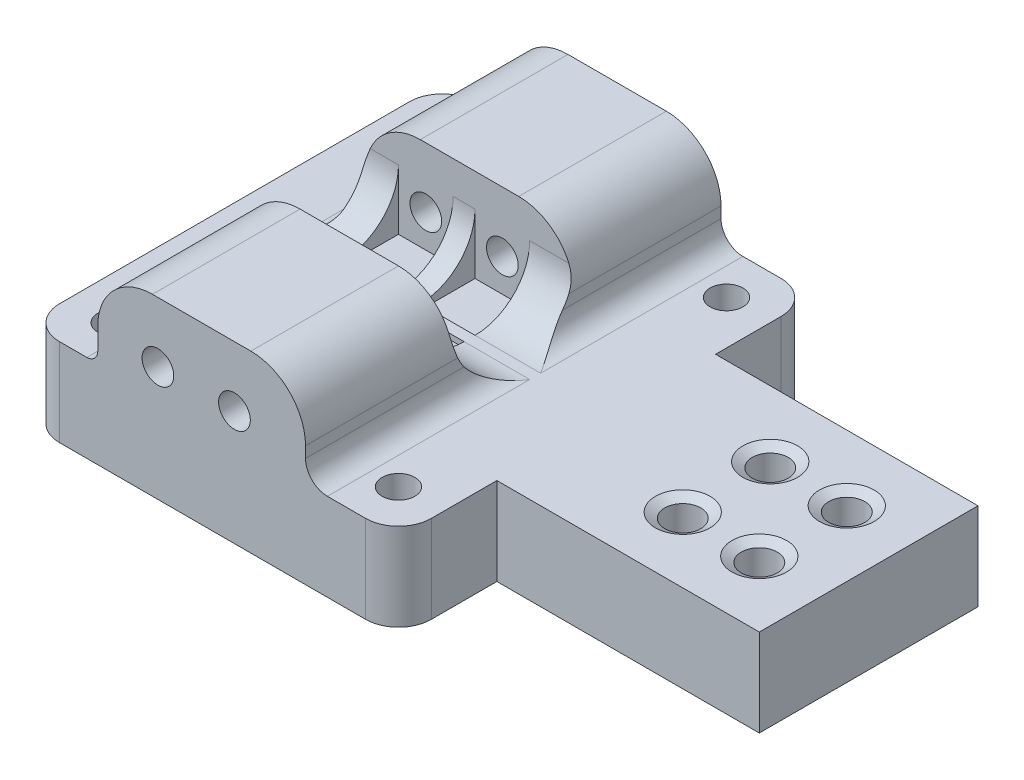
SolidWorks part; units mm, degrees
ref_plane "Front" through (0, 0, 0) normal (0, 0, 1) x (1, 0, 0)
ref_plane "Top" through (0, 0, 0) normal (0, 1, 0) x (1, 0, 0)
ref_plane "Right" through (0, 0, 0) normal (1, 0, 0) x (0, 0, -1)
sketch "Sketch1" plane through (0, 0, 0) normal (0, 1, 0) x (1, 0, 0)
  line L1 (0, 0) -> (300, 0)
  line L2 (0, 0) -> (0, -20)
  line L3 (0, -20) -> (300, -20)
  line L4 (300, 0) -> (300, -20)
  dimension "D1" = 20
  dimension "D2" = 300
extrude "Boss-Extrude1" add sketch "Sketch1" along normal blind 8
sketch "Sketch2" plane through (0, 0, 20) normal (0, 0, 1) x (1, 0, 0)
  line L0 (0, 8) -> (300, 8) construction
  line L1 (0, 0) -> (34, 0)
  line L2 (0, 0) -> (0, 8)
  line L3 (0, 8) -> (34, 8)
  line L4 (34, 0) -> (34, 8)
  line L5 (266, 8) -> (300, 8)
  line L6 (300, 0) -> (300, 8)
  line L7 (266, 0) -> (300, 0)
  line L8 (266, 0) -> (266, 8)
  dimension "D1" = 34
  dimension "D2" = 2
extrude "Boss-Extrude2" add sketch "Sketch2" along normal blind 9
sketch "Sketch3" plane through (0, 0, 0) normal (0, 0, -1) x (-1, 0, 0)
  line L0 (-300, 8) -> (0, 8) construction
  line L1 (0, 0) -> (-34, 0)
  line L2 (0, 0) -> (0, 8)
  line L3 (0, 8) -> (-34, 8)
  line L4 (-34, 0) -> (-34, 8)
  line L5 (-300, 0) -> (-300, 8)
  line L6 (-266, 8) -> (-300, 8)
  line L7 (-266, 0) -> (-266, 8)
  line L8 (-266, 0) -> (-300, 0)
  dimension "D1" = 34
  dimension "D2" = 2
extrude "Boss-Extrude3" add sketch "Sketch3" along normal blind 9
sketch "Sketch4" plane through (0, 8, 0) normal (0, 1, 0) x (1, 0, 0)
  line L0 (0, 9) -> (34, 9) construction
  line L1 (0, 9) -> (0, -29) construction
  circle A0 centre (4, 5) radius 1.5
  circle A1 centre (30, 5) radius 1.5
  circle A2 centre (30, -25) radius 1.5
  circle A3 centre (4, -25) radius 1.5
  circle A4 centre (296, -25) radius 1.5
  circle A5 centre (296, 5) radius 1.5
  circle A6 centre (270, -25) radius 1.5
  circle A7 centre (270, 5) radius 1.5
  dimension "D1" = 3
  dimension "D2" = 4
  dimension "D3" = 4
  dimension "D4" = 2
  dimension "D5" = 2
  dimension "D6" = 2
extrude "Cut-Extrude1" cut sketch "Sketch4" against normal through all
sketch "Sketch5" plane through (0, 0, 20) normal (0, 0, 1) x (1, 0, 0)
  line L0 (34, 8) -> (266, 8) construction
  line L1 (266, 0) -> (241, 0)
  line L2 (266, 0) -> (266, 8)
  line L3 (266, 8) -> (241, 8)
  line L4 (241, 0) -> (241, 8)
  dimension "D1" = 25
extrude "Boss-Extrude4" add sketch "Sketch5" along normal blind 17
sketch "Sketch6" plane through (0, 0, 0) normal (0, 0, -1) x (-1, 0, 0)
  line L0 (-266, 0) -> (-34, 0) construction
  line L1 (-266, 8) -> (-241, 8)
  line L2 (-266, 8) -> (-266, 0)
  line L3 (-266, 0) -> (-241, 0)
  line L4 (-241, 8) -> (-241, 0)
  dimension "D1" = 25
extrude "Boss-Extrude5" add sketch "Sketch6" along normal blind 17
sketch "Sketch12" plane through (0, 0, 37) normal (0, 0, 1) x (1, 0, 0)
  line L0 (241, 0) -> (266, 0) construction
  line L1 (241, 8) -> (249, 8)
  line L2 (241, 8) -> (241, 0)
  line L3 (241, 0) -> (249, 0)
  line L4 (249, 8) -> (249, 0)
  dimension "D1" = 8
extrude "Boss-Extrude7" add sketch "Sketch12" along normal blind 17
sketch "Sketch14" plane through (0, 0, 29) normal (0, 0, 1) x (1, 0, 0)
  line L0 (300, 8) -> (266, 8) construction
  line L1 (294.975, 8) -> (275, 8)
  line L2 (294.975, 8) -> (294.975, -5)
  line L3 (294.975, -5) -> (275, -4)
  line L4 (275, 8) -> (275, -4)
  line L7 (266, 8) -> (266, 0) construction
  dimension "D1" = 20
  dimension "D2" = 9
  dimension "D3" = 13
  dimension "D4" = 12
extrude "Boss-Extrude8" add sketch "Sketch14" along normal blind 12
sketch "Sketch15" plane through (294.975, 0, 0) normal (1, 0, 0) x (0, 0, -1)
  line L0 (-41, -5) -> (-41, 8) construction
  line L2 (-41, -5) -> (-29, -5) construction
  circle A0 centre (-35, 0) radius 1.6
  dimension "D1" = 3.2
  dimension "D2" = 6
  dimension "D3" = 5
extrude "Cut-Extrude7" cut sketch "Sketch15" against normal blind 20
sketch "Sketch16" plane through (0, 0, -9) normal (0, 0, -1) x (-1, 0, 0)
  line L0 (-266, 8) -> (-300, 8) construction
  line L1 (-295, 8) -> (-275, 8)
  line L2 (-295, 8) -> (-295, -5)
  line L3 (-295, -5) -> (-275, -5)
  line L4 (-275, 8) -> (-275, -5)
  line L6 (-266, 0) -> (-266, 8) construction
  dimension "D1" = 20
  dimension "D2" = 9
  dimension "D3" = 13
extrude "Boss-Extrude9" add sketch "Sketch16" along normal blind 12
sketch "Sketch17" plane through (295, 0, 0) normal (1, 0, 0) x (0, 0, -1)
  line L0 (21, -5) -> (9, -5) construction
  line L1 (21, 8) -> (21, -5) construction
  circle A0 centre (15, 0) radius 1.6
  dimension "D1" = 3.2
  dimension "D2" = 5
  dimension "D3" = 6
extrude "Cut-Extrude8" cut sketch "Sketch17" against normal blind 20
sketch "Sketch22" plane through (0, 8, 0) normal (0, 1, 0) x (1, 0, 0)
  line L0 (241, 17) -> (241, 0) construction
  line L1 (259, 9) -> (249, 9)
  line L2 (259, 9) -> (259, -29)
  line L3 (259, -29) -> (249, -29)
  line L4 (249, 9) -> (249, -29)
  line L5 (241, 17) -> (266, 17) construction
  line L6 (266, -37) -> (249, -37) construction
  dimension "D1" = 8
  dimension "D2" = 10
  dimension "D3" = 8
  dimension "D4" = 8
extrude "Cut-Extrude11" cut sketch "Sketch22" against normal through all
sketch "Sketch23" plane through (0, 0, 0) normal (0, -1, 0) x (-1, 0, 0)
  line L0 (-259, -29) -> (-259, 9) construction
  line L1 (-259, -19) -> (-267, -19)
  line L2 (-259, -19) -> (-259, -1)
  line L3 (-259, -1) -> (-267, -1)
  line L4 (-267, -19) -> (-267, -1)
  line L5 (-249, -29) -> (-259, -29) construction
  dimension "D1" = 8
  dimension "D2" = 10
  dimension "D3" = 10
extrude "Cut-Extrude12" cut sketch "Sketch23" against normal blind 4
sketch "Sketch24" plane through (259, 0, 0) normal (-1, 0, 0) x (0, 0, 1)
  line L0 (-9, 0) -> (-9, 8)
  line L1 (-9, 8) -> (-1, 8)
  line L2 (29, 8) -> (-9, 8) construction
  line L3 (-1, 8) -> (-9, 0)
  line L4 (29, 0) -> (29, 8)
  line L5 (29, 8) -> (21, 8)
  line L6 (21, 8) -> (29, 0)
  dimension "D1" = 8
  dimension "D2" = 8
extrude "Boss-Extrude12" add sketch "Sketch24" along normal blind 10
sketch "Sketch25" plane through (267, 0, 0) normal (-1, 0, 0) x (0, 0, 1)
  line L0 (19, 0) -> (19, 4)
  line L1 (19, 4) -> (15, 4)
  line L2 (1, 4) -> (19, 4) construction
  line L3 (15, 4) -> (19, 0)
  line L4 (1, 4) -> (5, 4)
  line L5 (5, 4) -> (1, 0)
  line L6 (1, 0) -> (1, 4)
  dimension "D1" = 4
  dimension "D2" = 4
extrude "Boss-Extrude13" add sketch "Sketch25" along normal blind 8
sketch "Sketch26" plane through (0, 8, 0) normal (0, 1, 0) x (1, 0, 0)
  line L0 (249, 1) -> (249, -21) construction
  line L1 (241, -54) -> (249, -54)
  line L2 (241, -54) -> (241, -6)
  line L3 (241, -6) -> (249, -6)
  line L4 (249, -54) -> (249, -6)
  dimension "D1" = 48
extrude "Boss-Extrude14" add sketch "Sketch26" along normal blind 14
sketch "Sketch27" plane through (0, 8, 0) normal (0, 1, 0) x (1, 0, 0)
  line L0 (249, -21) -> (259, -21) construction
  line L1 (249, -37) -> (257, -37)
  line L2 (249, -37) -> (249, -21)
  line L3 (249, -21) -> (257, -21)
  line L4 (257, -37) -> (257, -21)
  dimension "D1" = 8
extrude "Boss-Extrude15" add sketch "Sketch27" along normal blind 14
sketch "Sketch28" plane through (0, 0, 0) normal (0, -1, 0) x (1, 0, 0)
  line L0 (249, -9) -> (249, 29) construction
  line L1 (241, 54) -> (249, 54)
  line L2 (241, 54) -> (241, 14)
  line L3 (241, 14) -> (249, 14)
  line L4 (249, 54) -> (249, 14)
  dimension "D1" = 40
extrude "Cut-Extrude13" cut sketch "Sketch28" against normal blind 14
sketch "Sketch30" plane through (257, 0, 0) normal (1, 0, 0) x (0, 0, -1)
  line L0 (-37, 22) -> (-21, 22) construction
  line L1 (-21, 22) -> (-37, 22)
  line L2 (-21, 22) -> (-21, 8)
  line L3 (-21, 8) -> (-37, 8)
  line L4 (-37, 22) -> (-37, 8)
extrude "Boss-Extrude16" add sketch "Sketch30" along normal blind 9
sketch "Sketch31" plane through (0, 0, 0) normal (0, -1, 0) x (-1, 0, 0)
  line L1 (-249, -37) -> (-266, -37)
  line L2 (-249, -37) -> (-249, -29)
  line L3 (-249, -29) -> (-266, -29)
  line L4 (-266, -37) -> (-266, -29)
extrude "Cut-Extrude14" cut sketch "Sketch31" against normal blind 5
sketch "Sketch32" plane through (266, 0, 0) normal (1, 0, 0) x (0, 0, -1)
  line L0 (-37, 5) -> (-37, 22) construction
  line L1 (-21, 22) -> (-37, 22)
  line L2 (-21, 22) -> (-21, 13)
  line L3 (-21, 13) -> (-37, 13)
  line L4 (-37, 22) -> (-37, 13)
  dimension "D1" = 9
extrude "Cut-Extrude15" cut sketch "Sketch32" against normal blind 9
sketch "Sketch33" plane through (249, 0, 0) normal (-1, 0, 0) x (0, 0, 1)
  line L0 (29, 5) -> (24, 5)
  line L1 (21, 8) -> (29, 0) construction
  line L2 (24, 5) -> (29, 0)
  line L3 (29, 0) -> (29, 5)
extrude "Cut-Extrude16" cut sketch "Sketch33" against normal blind 10
sketch "Sketch34" plane through (0, 0, 29) normal (0, 0, 1) x (1, 0, 0)
  line L1 (266, 5) -> (259, 5)
  line L2 (266, 5) -> (266, 0)
  line L3 (266, 0) -> (259, 0)
  line L4 (259, 5) -> (259, 0)
extrude "Cut-Extrude17" cut sketch "Sketch34" against normal blind 5
sketch "Sketch35" plane through (0, 0, 21) normal (0, 0, -1) x (-1, 0, 0)
  line L0 (-249, 8) -> (-259, 8) construction
  line L1 (-259, 8) -> (-266, 8)
  line L2 (-259, 8) -> (-259, 13)
  line L3 (-259, 13) -> (-266, 13)
  line L4 (-266, 8) -> (-266, 13)
  line L5 (-266, 8) -> (-259, 8) construction
  line L6 (-266, 8) -> (-266, 13) construction
extrude "Boss-Extrude17" add sketch "Sketch35" along normal blind 5
sketch "Sketch36" plane through (0, 22, 0) normal (0, 1, 0) x (1, 0, 0)
  line L0 (241, -54) -> (249, -54) construction
  line L1 (249, -54) -> (249, -37) construction
  circle A0 centre (245, -50) radius 1.7
  circle A1 centre (245, -18) radius 1.7
  dimension "D1" = 3.4
  dimension "D2" = 4
  dimension "D3" = 4
  dimension "D4" = 2
extrude "Cut-Extrude18" cut sketch "Sketch36" against normal through all
sketch "Sketch37" plane through (0, 8, 0) normal (0, 1, 0) x (1, 0, 0)
  line L0 (241, -6) -> (171, -6)
  line L1 (241, -6) -> (241, -14) construction
  line L2 (241, -6) -> (241, -14)
  line L3 (241, -14) -> (241, -20) construction
  line L4 (241, -14) -> (171, -14)
  line L5 (171, -14) -> (171, -6)
  dimension "D1" = 70
extrude "Boss-Extrude18" add sketch "Sketch37" along normal blind 5
sketch "Sketch39" plane through (0, 8, 0) normal (0, 1, 0) x (1, 0, 0)
  line L0 (34, -20) -> (241, -20) construction
  line L1 (241, -14) -> (175, -14)
  line L2 (241, -14) -> (241, -20)
  line L3 (241, -20) -> (175, -20)
  line L4 (175, -14) -> (175, -20)
  dimension "D1" = 66
extrude "Cut-Extrude19" cut sketch "Sketch39" against normal through all
sketch "Sketch46" plane through (0, 8, 0) normal (0, 1, 0) x (1, 0, 0)
  line L1 (295, 9) -> (275, 9)
  line L2 (295, 9) -> (295, 21)
  line L3 (295, 21) -> (275, 21)
  line L4 (275, 9) -> (275, 21)
  line L5 (294.975, -41) -> (275, -41)
  line L6 (294.975, -41) -> (294.975, -29)
  line L7 (294.975, -29) -> (275, -29)
  line L8 (275, -41) -> (275, -29)
extrude "Boss-Extrude23" add sketch "Sketch46" along normal blind 10
sketch "Sketch47" plane through (0, 18, 0) normal (0, 1, 0) x (1, 0, 0)
  line L0 (295, 21) -> (275, 21) construction
  line L1 (275, 21) -> (303, 21)
  line L2 (275, 21) -> (275, 9)
  line L3 (275, 9) -> (303, 9)
  line L4 (303, 21) -> (303, 9)
  line L5 (275, 9) -> (295, 9) construction
  line L6 (294.975, -29) -> (275, -29) construction
  line L7 (274.975, -29) -> (303, -29)
  line L8 (274.975, -29) -> (274.975, -41)
  line L9 (274.975, -41) -> (303, -41)
  line L10 (303, -29) -> (303, -41)
  line L11 (275, -41) -> (294.975, -41) construction
  line L12 (275, 21) -> (275, 9) construction
  line L13 (295, 9) -> (295, 21) construction
  line L14 (275, -29) -> (275, -41) construction
  line L15 (294.975, -41) -> (294.975, -29) construction
  dimension "D1" = 28
  dimension "D2" = 20
  dimension "D3" = 28
  dimension "D4" = 20
extrude "Boss-Extrude24" add sketch "Sketch47" along normal blind 5 and the other way blind 5
sketch "Sketch48" plane through (303, 0, 0) normal (1, 0, 0) x (0, 0, -1)
  line L2 (-41, 13) -> (-41, 23) construction
  line L3 (21, 13) -> (21, 23) construction
  line L4 (9, 23) -> (21, 23) construction
  line L5 (-41, 23) -> (-29, 23) construction
  circle A0 centre (16, 18) radius 1.5
  circle A1 centre (-36, 18) radius 1.5
  dimension "D1" = 3
  dimension "D2" = 3
  dimension "D3" = 5
  dimension "D4" = 5
  dimension "D5" = 5
  dimension "D6" = 5
extrude "Cut-Extrude22" cut sketch "Sketch48" against normal blind 15
sketch "Sketch49" plane through (0, 8, 0) normal (0, 1, 0) x (1, 0, 0)
  line L0 (241, 0) -> (34, 0) construction
  line L1 (34, -20) -> (175, -20) construction
  line L2 (0, 9) -> (0, -29) construction
  circle A0 centre (78, -8) radius 1.45
  circle A1 centre (78, -12) radius 1.45
  dimension "D1" = 2.9
  dimension "D2" = 2.9
  dimension "D3" = 8
  dimension "D4" = 8
  dimension "D5" = 78
  dimension "D6" = 78
extrude "Cut-Extrude23" cut sketch "Sketch49" against normal through all
sketch "Sketch50" plane through (303, 0, 0) normal (1, 0, 0) x (0, 0, -1)
  line L1 (28.7085, 47.789) -> (-67.8332, 47.789)
  line L2 (28.7085, 47.789) -> (28.7085, -51.3705)
  line L3 (28.7085, -51.3705) -> (-67.8332, -51.3705)
  line L4 (-67.8332, 47.789) -> (-67.8332, -51.3705)
extrude "Cut-Extrude24" cut sketch "Sketch50" against normal blind 245
sketch "Sketch51" plane through (0, 8, 0) normal (0, 1, 0) x (1, 0, 0)
  line L1 (34, -20) -> (58, -20) construction
  line L2 (58, 0) -> (34, 0) construction
  line L4 (58, 0) -> (58, -20) construction
  circle A0 centre (52, -14) radius 1.65
  circle A1 centre (45, -14) radius 1.65
  circle A2 centre (45, -6) radius 1.65
  circle A3 centre (52, -6) radius 1.65
  dimension "D2" = 3.3
  dimension "D3" = 3.3
  dimension "D1" = 3.3
  dimension "D4" = 3.3
  dimension "D7" = 6
  dimension "D8" = 6
  dimension "D9" = 7
  dimension "D10" = 7
extrude "Cut-Extrude25" cut sketch "Sketch51" against normal through all
sketch "Sketch52" plane through (0, 8, 0) normal (0, 1, 0) x (1, 0, 0)
  line L0 (0, 9) -> (34, 9) construction
  line L1 (25.5, 9) -> (6.5, 9)
  line L2 (25.5, 9) -> (25.5, -4.5)
  line L3 (25.5, -4.5) -> (6.5, -4.5)
  line L4 (6.5, 9) -> (6.5, -4.5)
  line L5 (34, -29) -> (0, -29) construction
  line L6 (25.5, -29) -> (6.5, -29)
  line L7 (25.5, -29) -> (25.5, -15.5)
  line L8 (25.5, -15.5) -> (6.5, -15.5)
  line L9 (6.5, -29) -> (6.5, -15.5)
  line L10 (0, 9) -> (0, -29) construction
  dimension "D1" = 13.5
  dimension "D2" = 13.5
  dimension "D3" = 19
  dimension "D4" = 19
  dimension "D5" = 6.5
  dimension "D6" = 6.5
extrude "Boss-Extrude25" add sketch "Sketch52" along normal blind 8
fillet "Fillet1" radius 5 2 edges at (16, 8, 4.5) (16, 8, 15.5)
sketch "Sketch53" plane through (0, 0, -9) normal (0, 0, -1) x (-1, 0, 0)
  line L0 (-25.5, 16) -> (-6.5, 16) construction
  line L1 (-6.5, 16) -> (-6.5, 8) construction
  line L2 (-25.5, 16) -> (-25.5, 8) construction
  circle A0 centre (-19, 10.5) radius 1.45
  circle A1 centre (-12, 10.5) radius 1.45
  dimension "D1" = 2.9
  dimension "D2" = 2.9
  dimension "D3" = 5.5
  dimension "D4" = 5.5
  dimension "D5" = 5.5
  dimension "D6" = 6.5
extrude "Cut-Extrude26" cut sketch "Sketch53" against normal through all
fillet "Fillet2" radius 5 4 edges at (25.5, 16, 22.25) (6.5, 16, 22.25) (6.5, 16, -2.25) (25.5, 16, -2.25)
fillet "Fillet3" radius 3 4 edges at (34, 4, 29) (0, 4, 29) (0, 4, -9) (34, 4, -9)
sketch "Sketch54" plane through (0, 16, 0) normal (0, 1, 0) x (1, 0, 0)
  line L0 (11.5, -4.5) -> (20.5, -4.5) construction
  line L1 (16.5, -4.5) -> (21.5, -4.5)
  line L2 (16.5, -4.5) -> (16.5, -9.5)
  line L3 (16.5, -9.5) -> (21.5, -9.5)
  line L4 (21.5, -4.5) -> (21.5, -9.5)
  line L5 (20.5, -15.5) -> (11.5, -15.5) construction
  line L6 (14.5, -4.5) -> (9.5, -4.5)
  line L7 (14.5, -4.5) -> (14.5, -9.5)
  line L8 (14.5, -9.5) -> (9.5, -9.5)
  line L9 (9.5, -4.5) -> (9.5, -9.5)
  line L10 (16.5, -15.5) -> (21.5, -15.5)
  line L11 (16.5, -15.5) -> (16.5, -10.5)
  line L12 (16.5, -10.5) -> (21.5, -10.5)
  line L13 (21.5, -15.5) -> (21.5, -10.5)
  line L14 (11.5, 9) -> (11.5, -4.5) construction
  line L15 (14.5, -15.5) -> (9.5, -15.5)
  line L16 (14.5, -15.5) -> (14.5, -10.5)
  line L17 (14.5, -10.5) -> (9.5, -10.5)
  line L18 (9.5, -15.5) -> (9.5, -10.5)
  line L19 (20.5, -4.5) -> (20.5, 9) construction
  line L20 (11.5, -15.5) -> (11.5, -29) construction
  line L21 (20.5, -29) -> (20.5, -15.5) construction
  dimension "D1" = 5
  dimension "D2" = 5
  dimension "D3" = 5
  dimension "D4" = 5
  dimension "D5" = 3
  dimension "D6" = 4
  dimension "D7" = 5
  dimension "D8" = 5
  dimension "D9" = 5
  dimension "D10" = 5
  dimension "D11" = 3
  dimension "D12" = 4
extrude "Cut-Extrude27" cut sketch "Sketch54" against normal blind 8.5
fillet "Fillet4" radius 1 2 edges at (6.5, 8, 19.75) (6.5, 8, 0.25)
fillet "Fillet5" radius 2 2 edges at (25.5, 8, 19.75) (25.5, 8, 0.25)
sketch "Sketch55" plane through (0, 8, 0) normal (0, 1, 0) x (1, 0, 0)
  circle A0 centre (45, -6) radius 2.5
  circle A1 centre (52, -6) radius 2.5
  circle A2 centre (52, -14) radius 2.5
  circle A3 centre (45, -14) radius 2.5
  dimension "D1" = 5
  dimension "D2" = 5
  dimension "D3" = 5
  dimension "D4" = 5
extrude "Cut-Extrude28" cut sketch "Sketch55" against normal blind 2 draft 60
equation "\"滑动-垂直孔\" = 0.6"
equation "\"滑动-水平孔\"= 0.3"
equation "\"松动-垂直孔\" = 0.3"
equation "\"松动-水平孔\"= 0.1"
equation "\"正常-垂直孔\" = 0.15"
equation "\"正常-水平孔\"= 0"
equation "\"紧缩-垂直孔\"= 0"
equation "\"紧缩-水平孔\"= - 0.1"
equation "\"D1@Sketch51\"=\"松动-垂直孔\"+3"
equation "\"D4@Sketch51\"=\"松动-垂直孔\"+3"
equation "\"D3@Sketch51\"=\"松动-垂直孔\"+3"
equation "\"D2@Sketch51\"=\"松动-垂直孔\"+3"
equation "\"D1@Sketch4\"=\"紧缩-垂直孔\"+3"
equation "\"D1@Sketch53\"=\"紧缩-水平孔\"+3"
equation "\"D2@Sketch53\"=\"紧缩-水平孔\"+3"
